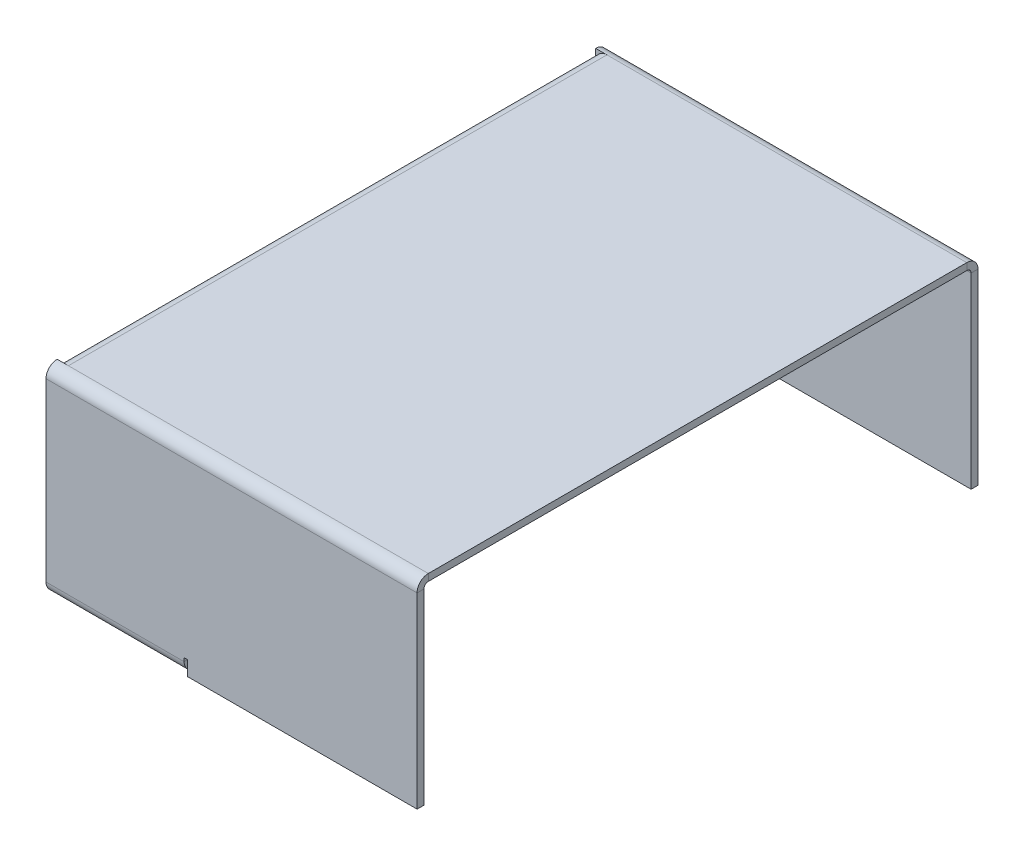
SolidWorks part; units mm, degrees
note: The reader was unsure of these and kept them because the rebuilt part matched: flange length of "边线-法兰1", "边线-法兰2", "边线-法兰3".
material "普通碳钢"
ref_plane "前视基准面" through (0, 0, 0) normal (0, 0, 1) x (1, 0, 0)
ref_plane "上视基准面" through (0, 0, 0) normal (0, 1, 0) x (1, 0, 0)
ref_plane "右视基准面" through (0, 0, 0) normal (1, 0, 0) x (0, 0, -1)
sketch "草图1" plane through (0, 0, 0) normal (0, 1, 0) x (1, 0, 0)
  line L0 (-142.2073, 0) -> (141.5917, 0) construction
  line L1 (0, 111.0325) -> (0, -123.0001) construction
  line L2 (0, 35.2089) -> (0, -29.7911)
  line L3 (0, -29.7911) -> (43, -29.7911)
  line L4 (43, -29.7911) -> (43, 35.2089)
  line L5 (43, 35.2089) -> (0, 35.2089)
  dimension "D1" = 65
  dimension "D2" = 43
base flange "基体-法兰1" sketch "草图1" thickness 0.8 reverse thickness direction no parameters "D1"=0.5
edge flange "边线-法兰1" sketch "草图10" flange profiles "草图10", "草图12" flange angle 90 flange length 23 flange position material inside bend radius 0.5 thickness 0.8 relief rectangular parameters "D6"=10, "D8"=1
bend "边线折弯2" bend radius 0.5 bend angle 90 parameters "D5"=1
bend "边线折弯3" bend radius 0.5 bend angle 90 parameters "D5"=2
sketch "草图10" plane through (0, -0.8, -35.2089) normal (0, 0, -1) x (1, 0, 0)
  line L0 (43, 0) -> (0, 0) construction
  line L1 (43, 0) -> (0, 0)
  line L2 (0, 0) -> (0, 22.2)
  line L3 (0, 22.2) -> (43, 22.2)
  line L4 (43, 22.2) -> (43, 0)
sketch "草图12" plane through (0, -0.8, 29.7911) normal (0, 0, 1) x (-1, 0, 0)
  line L0 (0, 0) -> (-43, 0) construction
  line L1 (0, 0) -> (-43, 0)
  line L2 (-43, 0) -> (-43, 22.2)
  line L3 (-43, 22.2) -> (0, 22.2)
  line L4 (0, 22.2) -> (0, 0)
edge flange "边线-法兰2" sketch "草图17" flange angle 90 flange length 8 flange position material inside bend radius 0.5 thickness 0.8 relief none parameters "D6"=10
sketch "草图17" plane through (0, -0.8, 0) normal (-1, 0, 0) x (0, 0, -1)
  line L0 (33.9089, 0) -> (-28.4911, 0) construction
  line L1 (33.9089, 0) -> (-28.4911, 0)
  line L2 (-28.4911, 0) -> (-28.4911, 7.2)
  line L3 (-28.4911, 7.2) -> (33.9089, 7.2)
  line L4 (33.9089, 7.2) -> (33.9089, 0)
  line L5 (33.9089, -0.8) -> (-28.4911, -0.8) construction
  line L6 (-29.7911, 0.5) -> (-29.7911, 22.2) construction
  line L7 (35.2089, 22.2) -> (35.2089, 0.5) construction
  circle A0 centre (-13.7911, 4.2) radius 1.25
  circle A1 centre (19.2089, 4.2) radius 1.25
  dimension "D2" = 2.5
  dimension "D1" = 8
  dimension "D3" = 16
  dimension "D4" = 3
  dimension "D5" = 16
  dimension "D6" = 3
bend "边线折弯5" bend radius 0.5 bend angle 90 parameters "D5"=3
edge flange "边线-法兰3" sketch "草图22" flange profiles "草图22", "草图23" flange angle 90 flange length 8.8 flange position material inside bend radius 0.5 thickness 0.8 relief rectangular parameters "D6"=10, "D8"=1
sketch "草图22" plane through (0, -23, -34.4089) normal (0, -1, 0) x (1, 0, 0)
  line L0 (43, 0) -> (0, 0) construction
  line L1 (16, 0) -> (0, 0)
  line L2 (0, 0) -> (0, 8)
  line L3 (0, 8) -> (16, 8)
  line L4 (16, 8) -> (16, 0)
  line L5 (0, -0.8) -> (0, 0) construction
  dimension "D1" = 0
  dimension "D2" = 8
  dimension "D3" = 16
sketch "草图23" plane through (0, -23, 28.9911) normal (0, -1, 0) x (-1, 0, 0)
  line L0 (0, 0) -> (-43, 0) construction
  line L1 (0, 0) -> (-16, 0)
  line L2 (-16, 0) -> (-16, 8)
  line L3 (-16, 8) -> (0, 8)
  line L4 (0, 8) -> (0, 0)
  line L5 (0, 62.9) -> (0, 0.5) construction
  dimension "D1" = 0
  dimension "D2" = 8
  dimension "D3" = 16
bend "边线折弯6" bend radius 0.5 bend angle 90 parameters "D5"=4
bend "边线折弯7" bend radius 0.5 bend angle 90 parameters "D5"=5
sketch "草图25" plane through (0, -22.2, 0) normal (0, 1, 0) x (1, 0, 0)
  line L0 (0, -29.7911) -> (16, -29.7911) construction
  line L3 (0, -28.4911) -> (0, -20.9911) construction
  line L4 (16, 35.2089) -> (0, 35.2089) construction
  line L5 (0, 26.4089) -> (0, 33.9089) construction
  circle A0 centre (9, -24.7911) radius 3.25
  circle A3 centre (9, 30.2089) radius 3.25
  dimension "D1" = 6.5
  dimension "D6" = 6.5
  dimension "D2" = 5
  dimension "D5" = 9
  dimension "D7" = 5
  dimension "D8" = 9
extrude "凸台-拉伸1" add sketch "草图25" along normal blind 2
hole_wizard "M3 螺纹孔1" positions "草图26" profile "草图27" tap size "M3" standard "GB" end condition up to next
sketch "草图26" plane through (0, -23, 0) normal (0, -1, 0) x (-1, 0, 0)
  point P0 (-9, -24.7911)
  point P10 (-9, 30.2089)
sketch "草图27" plane through (9, -23, 24.7911) normal (1, 0, 0) x (0, 0, -1)
  line L0 (0, 0) -> (0, 2.8)
  line L1 (0, 2.8) -> (1.25, 2.8)
  line L2 (1.25, 2.8) -> (1.25, 0)
  line L5 (1.25, 0) -> (0, 0)
  line L11 (0, -6.35) -> (0, 107.95) construction
  dimension "通孔螺纹孔钻头直径" = 2.5
  dimension "通孔螺纹孔钻头深度" = 2.8
cosmetic thread "孔螺蚊线2"
cosmetic thread "孔螺蚊线3"
fillet "圆角3" radius 5 4 edges at (16, -22.6, -26.4089) (0, -22.6, -26.4089) (0, -22.6, 20.9911) (16, -22.6, 20.9911)
sketch "折弯-线1" [suppressed] plane through (0, 0, 0) normal (0, 1, 0) x (1, 0, 0)
sketch "边界框1" [suppressed] plane through (0, 0, 0) normal (0, 1, 0) x (1, 0, 0)
sheet metal parameters "钣金6" thickness 0.8 parameters "D1"=0.5
flat pattern "平板型式6" [suppressed]
sketch "折弯-线2" plane through (0, 0, 0) normal (0, 1, 0) x (1, 0, 0)
sketch "边界框2" [suppressed] plane through (0, 0, 0) normal (0, 1, 0) x (1, 0, 0)
sheet metal parameters "钣金7" thickness 0.8 parameters "D1"=0.5
flat pattern "平板型式6" [suppressed]
sketch "折弯-线2" plane through (0, 0, 0) normal (0, 1, 0) x (1, 0, 0)
sketch "边界框2" [suppressed] plane through (0, 0, 0) normal (0, 1, 0) x (1, 0, 0)
bend of the flat pattern "展开-<边线折弯2>1"
bend of the flat pattern "展开-<边线折弯3>1"
sheet metal parameters "钣金8" thickness 0.8 parameters "D1"=0.5
flat pattern "平板型式6" [suppressed]
sketch "折弯-线2" plane through (0, 0, 0) normal (0, 1, 0) x (1, 0, 0)
sketch "边界框2" [suppressed] plane through (0, 0, 0) normal (0, 1, 0) x (1, 0, 0)
bend of the flat pattern "展开-<边线折弯2>1"
bend of the flat pattern "展开-<边线折弯3>1"
bend of the flat pattern "展开-<边线折弯5>1"
sheet metal parameters "钣金9" thickness 0.8 parameters "D1"=0.5
flat pattern "平板型式6" [suppressed]
sketch "折弯-线2" plane through (0, 0, 0) normal (0, 1, 0) x (1, 0, 0)
  line L0 (5, -49.0116) -> (40, -49.0116) construction
  line L1 (40, 54.4295) -> (5, 54.4295) construction
  line L2 (0, -29.1979) -> (40, -29.1979) construction
  line L3 (40, 34.6158) -> (0, 34.6158) construction
  line L4 (5, -49.0116) -> (40, -49.0116) construction
  line L5 (40, 54.4295) -> (5, 54.4295) construction
  line L6 (0, -29.1979) -> (40, -29.1979) construction
  line L7 (40, 34.6158) -> (0, 34.6158) construction
sketch3d "边界框2" [suppressed]
  line L0 (0, 59.9364, 0) -> (0, -54.5185, 0) construction
  line L1 (40, 59.9364, 0) -> (40, -54.5185, 0) construction
  line L2 (0, 59.9364, 0) -> (40, 59.9364, 0) construction
  line L3 (0, -54.5185, 0) -> (40, -54.5185, 0) construction
bend of the flat pattern "展开-<边线折弯2>1"
bend of the flat pattern "展开-<边线折弯3>1"
bend of the flat pattern "展开-<边线折弯6>1"
bend of the flat pattern "展开-<边线折弯7>1"
bend of the flat pattern "展开-<边线折弯5>2"
sheet metal parameters "钣金11" thickness 0.8 parameters "D1"=0.5
flat pattern "平板型式6" [suppressed]
sketch "折弯-线2" plane through (0, 0, 0) normal (0, 1, 0) x (1, 0, 0)
  line L0 (5, -49.0116) -> (40, -49.0116) construction
  line L1 (40, 54.4295) -> (5, 54.4295) construction
  line L2 (0, -29.1979) -> (40, -29.1979) construction
  line L3 (40, 34.6158) -> (0, 34.6158) construction
  line L4 (5, -49.0116) -> (40, -49.0116) construction
  line L5 (40, 54.4295) -> (5, 54.4295) construction
  line L6 (0, -29.1979) -> (40, -29.1979) construction
  line L7 (40, 34.6158) -> (0, 34.6158) construction
sketch3d "边界框2" [suppressed]
  line L0 (0, 59.9364, 0) -> (0, -54.5185, 0) construction
  line L1 (40, 59.9364, 0) -> (40, -54.5185, 0) construction
  line L2 (0, 59.9364, 0) -> (40, 59.9364, 0) construction
  line L3 (0, -54.5185, 0) -> (40, -54.5185, 0) construction
bend of the flat pattern "展开-<边线折弯2>1"
bend of the flat pattern "展开-<边线折弯3>1"
bend of the flat pattern "展开-<边线折弯6>1"
bend of the flat pattern "展开-<边线折弯7>1"
bend of the flat pattern "展开-<边线折弯5>2"
sheet metal parameters "钣金12" thickness 0.8 parameters "D1"=0.5
flat pattern "平板型式6"
sketch "折弯-线2" plane through (0, 0, 0) normal (0, 1, 0) x (1, 0, 0)
  line L0 (0, -49.0116) -> (14, -49.0116) construction
  line L1 (44, 54.4295) -> (30, 54.4295) construction
  line L2 (0, -29.1979) -> (44, -29.1979) construction
  line L3 (44, 34.6158) -> (0, 34.6158) construction
  line L4 (0, -49.0116) -> (14, -49.0116) construction
  line L5 (44, 54.4295) -> (30, 54.4295) construction
  line L6 (0, -29.1979) -> (44, -29.1979) construction
  line L7 (44, 34.6158) -> (0, 34.6158) construction
  line L8 (0.5931, 33.9089) -> (0.5931, -28.4911) construction
  line L9 (30, -49.0116) -> (44, -49.0116) construction
  line L10 (14, 54.4295) -> (0, 54.4295) construction
  line L11 (0.5931, 33.9089) -> (0.5931, -28.4911) construction
sketch3d "边界框2" [suppressed]
  line L0 (-6.8137, 62.6364, 0) -> (-6.8137, -57.2185, 0) construction
  line L1 (44, 62.6364, 0) -> (44, -57.2185, 0) construction
  line L2 (-6.8137, 62.6364, 0) -> (44, 62.6364, 0) construction
  line L3 (-6.8137, -57.2185, 0) -> (44, -57.2185, 0) construction
bend of the flat pattern "展开-<边线折弯2>1"
bend of the flat pattern "展开-<边线折弯3>1"
bend of the flat pattern "展开-<边线折弯6>1"
bend of the flat pattern "展开-<边线折弯7>1"
bend of the flat pattern "展开-<边线折弯5>2"
